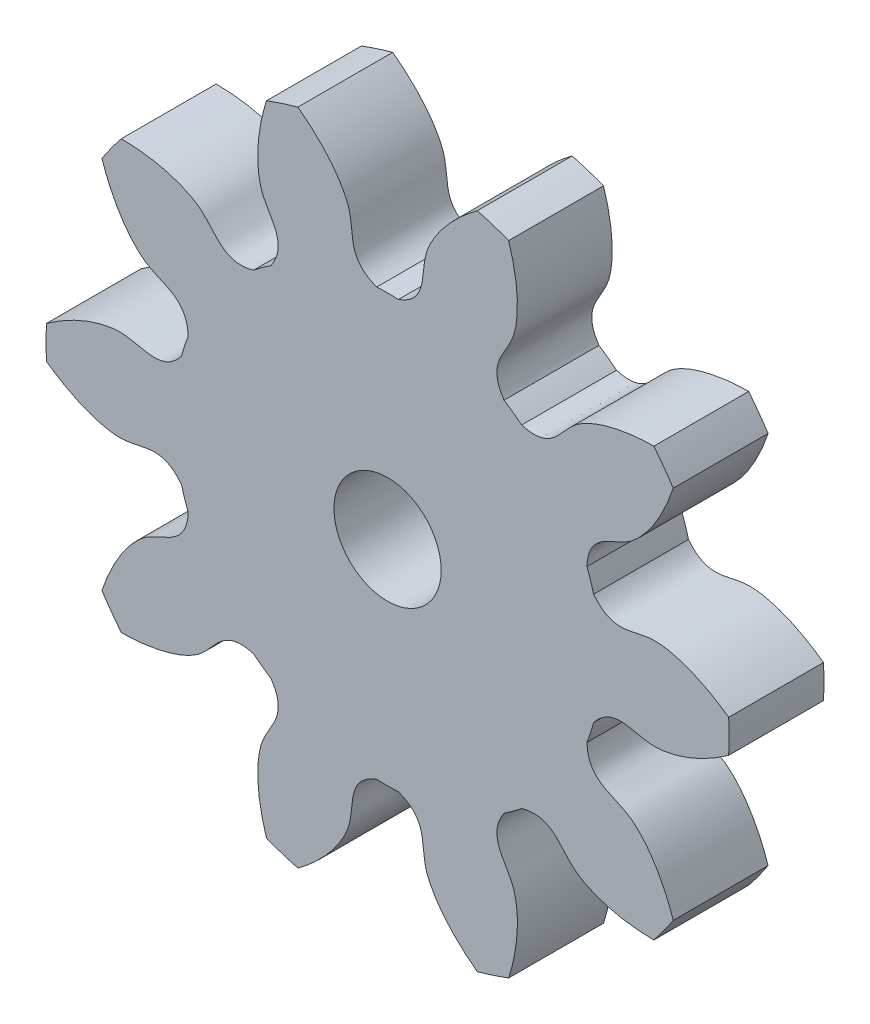
SolidWorks part; units mm, degrees
ref_plane "前视基准面" through (0, 0, 0) normal (0, 0, 1) x (1, 0, 0)
ref_plane "上视基准面" through (0, 0, 0) normal (0, 1, 0) x (1, 0, 0)
ref_plane "右视基准面" through (0, 0, 0) normal (1, 0, 0) x (0, 0, -1)
sketch "草图1" plane through (0, 0, 0) normal (0, 0, 1) x (1, 0, 0)
  circle A0 centre (0, 0) radius 3.6
extrude "凸台-拉伸1" add sketch "草图1" along normal blind 1
ref_axis "基准轴1" through (0, 0, -1.5) along (0, 0, 1)
sketch "草图2" plane through (0, 0, 0) normal (0, 0, 1) x (1, 0, 0)
  line L0 (0, 0) -> (0, 3.6) construction
  circle A0 centre (0, 0) radius 3.6 construction
  arc A1 (0.1143, 2.2471) -> (-0.1143, 2.2471) centre (0, 0) ccw
  arc A2 (2.5522, 4.0166) -> (-2.5522, 4.0166) centre (0, 0) ccw
  spline S0 degree 3 poles (0.1143, 2.2471) (0.4353, 2.3643) (0.3443, 2.6224) (0.4132, 2.8348) (0.4167, 2.8449) (0.4208, 2.856) (0.4255, 2.8681) (0.4309, 2.8811) (0.437, 2.8951) (0.4439, 2.9099) (0.4516, 2.9256) (0.46, 2.9422) (0.4694, 2.9596) (0.4796, 2.9778) (0.4908, 2.9967) (0.5029, 3.0164) (0.5161, 3.0367) (0.5303, 3.0578) (0.5455, 3.0795) (0.5619, 3.1017) (0.5793, 3.1246) (0.598, 3.1479) (0.6178, 3.1718) (0.6388, 3.1961) (0.661, 3.2208) (0.6846, 3.2459) (0.7094, 3.2713) (0.7355, 3.2971) (0.7629, 3.323) (0.7917, 3.3492) (0.8219, 3.3755) (0.8534, 3.402) (0.8863, 3.4285) (0.9207, 3.455) (0.9565, 3.4816) (0.9937, 3.508) (1.0324, 3.5344) (1.0725, 3.5606) (1.1142, 3.5865) (1.1572, 3.6122) (1.2018, 3.6376) (1.2479, 3.6627) (1.2955, 3.6873) (1.3445, 3.7115) (1.3951, 3.7351) (1.4471, 3.7583) (1.5007, 3.7808) (1.5557, 3.8026) (1.6122, 3.8237) (1.6702, 3.8441) (1.7296, 3.8637) (1.7905, 3.8824) (1.8529, 3.9002) (1.9167, 3.917) (1.9819, 3.9328) (2.0485, 3.9475) (2.1165, 3.9612) (2.1859, 3.9737) (2.2566, 3.9849) (2.3286, 3.9949) (2.4272, 4.0066) (2.5019, 4.0132) (2.5522, 4.0166) knots 0 0 0 0 0.201721 0.204697 0.208023 0.211699 0.215726 0.220102 0.224829 0.229906 0.235332 0.241109 0.247237 0.253714 0.260541 0.267719 0.275246 0.283124 0.291352 0.29993 0.308858 0.318136 0.327765 0.337743 0.348072 0.358751 0.36978 0.381158 0.392888 0.404967 0.417396 0.430176 0.443305 0.456785 0.470615 0.484795 0.499325 0.514205 0.529435 0.545016 0.560946 0.577227 0.593858 0.610839 0.62817 0.645851 0.663882 0.682264 0.700995 0.720077 0.739509 0.759291 0.779423 0.799905 0.820737 0.84192 0.863452 0.885335 0.907568 0.930151 0.953084 1 1 1 1
  spline S1 degree 3 poles (-0.1143, 2.2471) (-0.4353, 2.3643) (-0.3443, 2.6224) (-0.4132, 2.8348) (-0.4167, 2.8449) (-0.4208, 2.856) (-0.4255, 2.8681) (-0.4309, 2.8811) (-0.437, 2.8951) (-0.4439, 2.9099) (-0.4516, 2.9256) (-0.46, 2.9422) (-0.4694, 2.9596) (-0.4796, 2.9778) (-0.4908, 2.9967) (-0.5029, 3.0164) (-0.5161, 3.0367) (-0.5303, 3.0578) (-0.5455, 3.0795) (-0.5619, 3.1017) (-0.5793, 3.1246) (-0.598, 3.1479) (-0.6178, 3.1718) (-0.6388, 3.1961) (-0.661, 3.2208) (-0.6846, 3.2459) (-0.7094, 3.2713) (-0.7355, 3.2971) (-0.7629, 3.323) (-0.7917, 3.3492) (-0.8219, 3.3755) (-0.8534, 3.402) (-0.8863, 3.4285) (-0.9207, 3.455) (-0.9565, 3.4816) (-0.9937, 3.508) (-1.0324, 3.5344) (-1.0725, 3.5606) (-1.1142, 3.5865) (-1.1572, 3.6122) (-1.2018, 3.6376) (-1.2479, 3.6627) (-1.2955, 3.6873) (-1.3445, 3.7115) (-1.3951, 3.7351) (-1.4471, 3.7583) (-1.5007, 3.7808) (-1.5557, 3.8026) (-1.6122, 3.8237) (-1.6702, 3.8441) (-1.7296, 3.8637) (-1.7905, 3.8824) (-1.8529, 3.9002) (-1.9167, 3.917) (-1.9819, 3.9328) (-2.0485, 3.9475) (-2.1165, 3.9612) (-2.1859, 3.9737) (-2.2566, 3.9849) (-2.3286, 3.9949) (-2.4272, 4.0066) (-2.5019, 4.0132) (-2.5522, 4.0166) knots 0 0 0 0 0.201721 0.204697 0.208023 0.211699 0.215726 0.220102 0.224829 0.229906 0.235332 0.241109 0.247237 0.253714 0.260541 0.267719 0.275246 0.283124 0.291352 0.29993 0.308858 0.318136 0.327765 0.337743 0.348072 0.358751 0.36978 0.381158 0.392888 0.404967 0.417396 0.430176 0.443305 0.456785 0.470615 0.484795 0.499325 0.514205 0.529435 0.545016 0.560946 0.577227 0.593858 0.610839 0.62817 0.645851 0.663882 0.682264 0.700995 0.720077 0.739509 0.759291 0.779423 0.799905 0.820737 0.84192 0.863452 0.885335 0.907568 0.930151 0.953084 1 1 1 1
extrude "切除-拉伸1" cut sketch "草图2" along normal through all
pattern_circular "阵列(圆周)1" count 10 every 36 about axis through (0, 0, -1.5) along (0, 0, 1) of "切除-拉伸1"
sketch "草图3" plane through (0, 0, 0) normal (0, 0, 1) x (1, 0, 0)
  circle A0 centre (0, 0) radius 3 construction
  dimension "Dn" = 6
sketch "草图4" plane through (0, 0, 1) normal (0, 0, 1) x (1, 0, 0)
  circle A0 centre (0, 0) radius 0.565
  dimension "D1" = 1.13
extrude "切除-拉伸2" cut sketch "草图4" against normal through all
